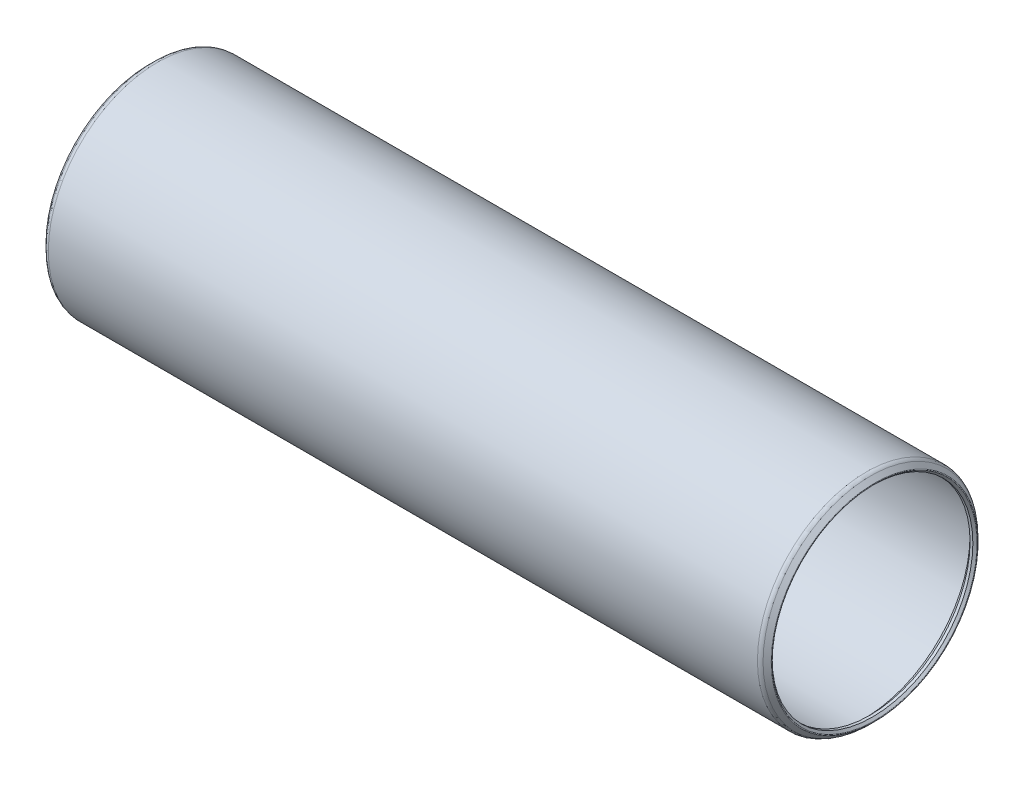
SolidWorks part; units mm, degrees
material "AISI 1045 Steel, cold drawn"
ref_plane "Front Plane" through (0, 0, 0) normal (0, 0, 1) x (1, 0, 0)
ref_plane "Top Plane" through (0, 0, 0) normal (0, 1, 0) x (1, 0, 0)
ref_plane "Right Plane" through (0, 0, 0) normal (1, 0, 0) x (0, 0, -1)
ref_plane "Plane1" through (129.6035, 0, 0) normal (1, 0, 0) x (0, 0, -1)
sketch "Sketch1" plane through (0, 0, 0) normal (0, 0, 1) x (1, 0, 0)
  line L0 (-0.8826, 18.5547) -> (-0.508, 18.1801)
  line L1 (-0.508, 18.1801) -> (0, 18.1801)
  line L2 (0, 18.1801) -> (1.016, 19.196)
  line L3 (1.016, 19.196) -> (128.5875, 19.196)
  line L4 (128.5875, 19.196) -> (129.6035, 18.1801)
  line L5 (129.6035, 18.1801) -> (130.1115, 18.1801)
  line L6 (130.1115, 18.1801) -> (130.4861, 18.5547)
  line L7 (130.4861, 18.7343) -> (129.7504, 19.47)
  line L8 (129.032, 19.7675) -> (0.5715, 19.7675)
  line L9 (-0.1469, 19.47) -> (-0.8826, 18.7343)
  line L10 (129.6035, 0) -> (0, 0) construction
  arc A0 (-0.8826, 18.7343) -> (-0.8826, 18.5547) centre (-0.7928, 18.6445) ccw
  arc A1 (130.4861, 18.5547) -> (130.4861, 18.7343) centre (130.3963, 18.6445) ccw
  arc A2 (129.7504, 19.47) -> (129.032, 19.7675) centre (129.032, 18.7515) ccw
  arc A3 (0.5715, 19.7675) -> (-0.1469, 19.47) centre (0.5715, 18.7515) ccw
revolve "Revolve1" add sketch "Sketch1" angle 360 about L10 reverse direction yes
ref_plane "Plane2" through (64.8017, 0, 0) normal (1, 0, 0) x (0, 0, -1)
ref_plane "cp1 XY" through (64.8017, 0, 0) normal (1, 0, 0) x (0, 0, -1)
ref_plane "cp1 XZ" through (0, 19.7676, 0) normal (0, -1, 0) x (-1, 0, 0)
ref_plane "cp1 YZ" through (0, 0, 0) normal (0, 0, -1) x (-1, 0, 0)
ref_axis "cp1 X" through (64.8017, 19.7676, 80.9) along (0, 0, -1)
ref_axis "cp1 Y" through (64.8017, -50, 0) along (0, 1, 0)
ref_axis "cp1 Z" through (80.9, 19.7676, 0) along (-1, 0, 0)
sketch3d "cp1"
  point P0 (64.8017, 19.7676, 0)
ref_plane "cp2 XY" through (64.8017, 0, 0) normal (1, 0, 0) x (0, 0, -1)
ref_plane "cp2 XZ" through (0, 0, 0) normal (0, -1, 0) x (-1, 0, 0)
ref_plane "cp2 YZ" through (0, 0, -19.7676) normal (0, 0, -1) x (-1, 0, 0)
ref_axis "cp2 X" through (64.8017, 0, 80.9) along (0, 0, -1)
ref_axis "cp2 Y" through (64.8017, -50, -19.7676) along (0, 1, 0)
ref_axis "cp2 Z" through (80.9, 0, -19.7676) along (-1, 0, 0)
sketch3d "cp2"
  point P0 (64.8017, 0, -19.7676)
ref_plane "cp3 XY" through (64.8017, 0, 0) normal (1, 0, 0) x (0, 0, -1)
ref_plane "cp3 XZ" through (0, -19.7676, 0) normal (0, -1, 0) x (-1, 0, 0)
ref_plane "cp3 YZ" through (0, 0, 0) normal (0, 0, -1) x (-1, 0, 0)
ref_axis "cp3 X" through (64.8017, -19.7676, 80.9) along (0, 0, -1)
ref_axis "cp3 Y" through (64.8017, -50, 0) along (0, 1, 0)
ref_axis "cp3 Z" through (80.9, -19.7676, 0) along (-1, 0, 0)
sketch3d "cp3"
  point P0 (64.8017, -19.7676, 0)
ref_plane "cp4 XY" through (64.8017, 0, 0) normal (1, 0, 0) x (0, 0, -1)
ref_plane "cp4 XZ" through (0, 0, 0) normal (0, -1, 0) x (-1, 0, 0)
ref_plane "cp4 YZ" through (0, 0, 19.7676) normal (0, 0, -1) x (-1, 0, 0)
ref_axis "cp4 X" through (64.8017, 0, 80.9) along (0, 0, -1)
ref_axis "cp4 Y" through (64.8017, -50, 19.7676) along (0, 1, 0)
ref_axis "cp4 Z" through (80.9, 0, 19.7676) along (-1, 0, 0)
sketch3d "cp4"
  point P0 (64.8017, 0, 19.7676)
ref_plane "tube_front XY" through (0, 0, 0) normal (1, 0, 0) x (0, 0, -1)
ref_plane "tube_front XZ" through (0, 0, 0) normal (0, -1, 0) x (-1, 0, 0)
ref_plane "tube_front YZ" through (0, 0, 0) normal (0, 0, -1) x (-1, 0, 0)
ref_axis "tube_front X" through (0, 0, 80.9) along (0, 0, -1)
ref_axis "tube_front Y" through (0, -50, 0) along (0, 1, 0)
ref_axis "tube_front Z" through (80.9, 0, 0) along (-1, 0, 0)
sketch3d "tube_front"
  point P0 (0, 0, 0)
ref_plane "tube_rear XY" through (129.6035, 0, 0) normal (1, 0, 0) x (0, 0, -1)
ref_plane "tube_rear XZ" through (0, 0, 0) normal (0, -1, 0) x (-1, 0, 0)
ref_plane "tube_rear YZ" through (0, 0, 0) normal (0, 0, -1) x (-1, 0, 0)
ref_axis "tube_rear X" through (129.6035, 0, 80.9) along (0, 0, -1)
ref_axis "tube_rear Y" through (129.6035, -50, 0) along (0, 1, 0)
ref_axis "tube_rear Z" through (80.9, 0, 0) along (-1, 0, 0)
sketch3d "tube_rear"
  point P0 (129.6035, 0, 0)
